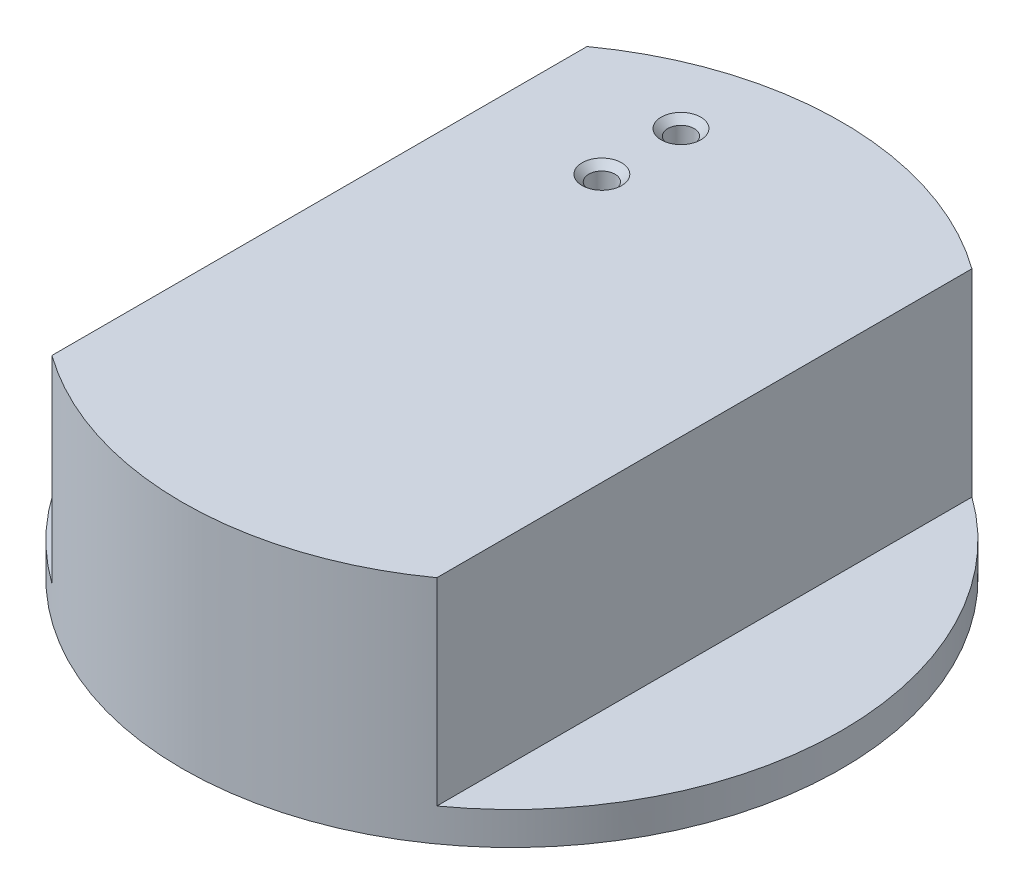
SolidWorks part; units mm, degrees
ref_plane "Ön Düzlem" through (0, 0, 0) normal (0, 0, 1) x (1, 0, 0)
ref_plane "Üst Düzlem" through (0, 0, 0) normal (0, 1, 0) x (1, 0, 0)
ref_plane "Sağ Düzlem" through (0, 0, 0) normal (1, 0, 0) x (0, 0, -1)
sketch "Çizim1" plane through (0, 0, 0) normal (0, 1, 0) x (1, 0, 0)
  line L0 (0, 0) -> (0, 50) construction
  line L1 (-29.199, 40.5884) -> (-29.199, -40.5884)
  line L2 (-47.199, 16.5) -> (-29.199, 16.5)
  line L3 (-47.199, 16.5) -> (-47.199, -16.5)
  line L4 (-47.199, -16.5) -> (-29.199, -16.5)
  line L5 (-29.199, 16.5) -> (-29.199, -16.5)
  line L6 (29.199, 40.5884) -> (29.199, -40.5884)
  line L7 (47.199, -16.5) -> (29.199, -16.5)
  line L8 (29.199, 16.5) -> (29.199, -16.5)
  line L9 (47.199, 16.5) -> (29.199, 16.5)
  line L10 (47.199, 16.5) -> (47.199, -16.5)
  circle A0 centre (0, 0) radius 50
  point P8 (-29.199, 0)
  dimension "D1" = 100
  dimension "D2" = 18
  dimension "D3" = 33
extrude "base" add sketch "Çizim1" against normal blind 5 contours L1 A0 L2 | L3 A0 | L3 L4 L1 L2 | L4 A0 L1 | L6 A0 L1 | L6 A0 L7 | L10 L9 L6 L7 | L9 A0 L6 | L10 A0 region at (0, 0, 0) region at (-35.8614, 0, -25.3381) region at (-38.199, 0, 0) region at (35.8614, 0, -25.3381) region at (-48.3222, 0, 0) region at (-35.8614, 0, 25.3381) region at (38.199, 0, 0) region at (48.3222, 0, 0) region at (35.8614, 0, 25.3381)
extrude "Yükseklik-Ekstrüzyon2" add sketch "Çizim1<3>" along normal blind 30 contours L6 A0 L1 region at (0, 0, 0)
sketch "Çizim1<3>" plane through (0, 0, 0) normal (0, 1, 0) x (1, 0, 0) same geometry as "Çizim1"
sketch "Çizim2" plane through (0, 30, 0) normal (0, 1, 0) x (1, 0, 0)
  line L0 (-11.3, 30.9428) -> (29.199, 30.9428) construction
  line L2 (29.199, 40.5884) -> (29.199, -40.5884) construction
  circle A1 centre (-11.3, 36.9428) radius 2
  circle A2 centre (-11.3, 24.9428) radius 2
  point P3 (29.199, 23.9715)
  point P7 (-19.2262, 0)
  point P11 (-11.3, 36.9428)
  point P13 (-11.3, 16.9428)
  dimension "D1" = 4
  dimension "D2" = 6
extrude "banana slotu" cut sketch "Çizim2" against normal through all
chamfer "Pah1" distance 1 angle 45 2 edges at (-11.3, 30, -34.9428) (-11.3, 30, -26.9428)
